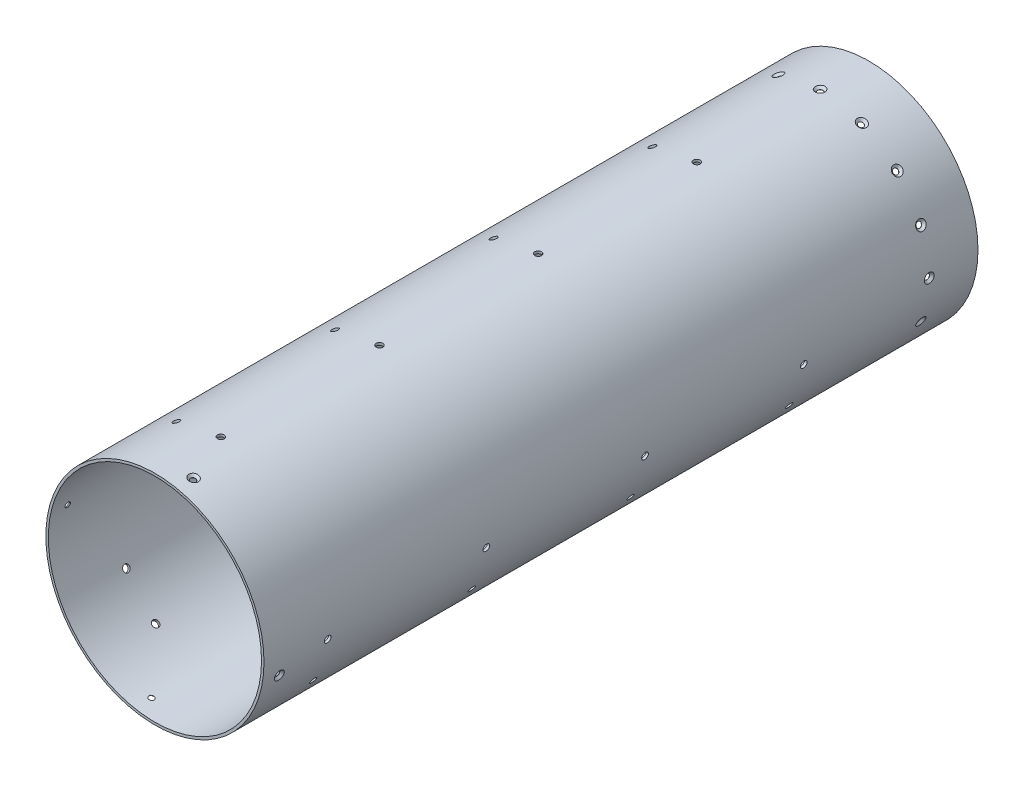
SolidWorks part; units mm, degrees
material "6061-T6 (SS)"
ref_plane "Front Plane" through (0, 0, 0) normal (0, 0, 1) x (1, 0, 0)
ref_plane "Top Plane" through (0, 0, 0) normal (0, 1, 0) x (1, 0, 0)
ref_plane "Right Plane" through (0, 0, 0) normal (1, 0, 0) x (0, 0, -1)
sketch "Sketch1" plane through (0, 0, 0) normal (0, 0, 1) x (1, 0, 0)
  circle A0 centre (0, 0) radius 69.85
  circle A1 centre (0, 0) radius 68.2625
  dimension "D1" = 139.7
  dimension "D2" = 1.5875
extrude "Extrude1" add sketch "Sketch1" along normal blind 457.2
ref_plane "Plane1" through (0, 0, 31.242) normal (0, 0, -1) x (-1, 0, 0)
sketch "Sketch2" plane through (0, 0, 31.242) normal (0, 0, -1) x (-1, 0, 0)
  line L0 (0, 0) -> (0, -69.85) construction
  line L1 (0, 0) -> (-13.6271, -68.5079) construction
  circle A0 centre (0, 0) radius 69.85 construction
  circle A1 centre (0, 0) radius 69.85 construction
  dimension "D1" = 11.25
ref_plane "Plane2" through (0, -69.85, 31.242) normal (0, -1, 0) x (1, 0, 0)
hole_wizard "CSK for M3 Flat Head Machine Screw1" positions "Sketch5" profile "Sketch4" countersink size "M3" standard "Ansi Metric" end condition through all
sketch "Sketch5" plane through (0, -69.85, 31.242) normal (0, -1, 0) x (1, 0, 0)
  point P2 (0, 0)
sketch "Sketch4" plane through (0, -69.85, 31.242) normal (1, 0, 0) x (0, 0, -1)
  line L0 (0, 0) -> (0, 161.1134)
  line L1 (0, 161.1134) -> (1.7, 161.1134)
  line L2 (1.7, 161.1134) -> (1.7, 1.45)
  line L3 (1.7, 1.45) -> (3.15, 0)
  line L5 (3.15, 0) -> (0, 0)
  line L6 (-1.7, 1.45) -> (-3.15, 0) construction
  line L11 (0, -6.35) -> (0, 107.95) construction
  dimension "Thru Hole Dia." = 3.4
  dimension "Thru Hole Depth" = 161.1134
  dimension "Near C'Sink Dia." = 6.3
  dimension "Near C'Sink Angle" = 90
pattern_circular "CirPattern1" count 16 over 360 about axis through (0, 0, 457.2) along (0, 0, -1) of "CSK for M3 Flat Head Machine Screw1"
ref_plane "Plane3" through (0, 0, 446.0875) normal (0, 0, 1) x (1, 0, 0)
ref_plane "Plane5" through (0, 0, 0) normal (0.8315, 0.5556, 0) x (-0.5556, 0.8315, 0)
ref_plane "Plane7" through (0, 0, 0) normal (0.5556, -0.8315, 0) x (0.8315, 0.5556, 0)
ref_plane "Plane9" through (0, 0, 0) normal (-0.1951, -0.9808, 0) x (0.9808, -0.1951, 0)
sketch "Sketch7" plane through (0, 0, 457.2) normal (0, 0, 1) x (1, 0, 0)
  circle A0 centre (0, 0) radius 69.85 construction
  point P0 (69.85, 0)
ref_plane "Plane10" through (13.6271, -68.5079, 31.242) normal (0.1951, -0.9808, 0) x (0.9808, 0.1951, 0)
hole_wizard "#10 Clearance Hole1" positions "Sketch12" profile "Sketch11" hole size "#10" standard "Ansi Inch"
sketch "Sketch12" plane through (13.6271, -68.5079, 31.242) normal (0.1951, -0.9808, 0) x (0.9808, 0.1951, 0)
  point P1 (0, 0)
sketch "Sketch11" plane through (13.6271, -68.5079, 31.242) normal (0, 0, 1) x (0.9808, 0.1951, 0)
  line L0 (0, 0) -> (0, 14.2338)
  line L1 (0, 14.2338) -> (2.5527, 12.7)
  line L2 (2.5527, 12.7) -> (2.5527, 0)
  line L5 (2.5527, 0) -> (0, 0)
  line L10 (0, 14.2338) -> (-2.5527, 12.7) construction
  line L11 (0, -6.35) -> (0, 107.95) construction
  dimension "Hole Dia." = 5.1054
  dimension "Hole Depth" = 12.7
  dimension "Drill Angle" = 118
sketch "Sketch13" plane through (13.6271, -68.5079, 31.242) normal (0.1951, -0.9808, 0) x (0.9808, 0.1951, 0)
  line L0 (0, 0) -> (0, 20.3882) construction
ref_plane "Plane11" through (0, 0, 0) normal (0.9808, 0.1951, 0) x (0, 0, -1)
ref_plane "Plane12" through (0, 0, 446.0748) normal (0, 0, 1) x (1, 0, 0)
sketch "Sketch15" plane through (0, 0, 446.0748) normal (0, 0, 1) x (1, 0, 0)
  line L0 (0, 0) -> (13.6271, 68.5079) construction
  line L2 (0, 0) -> (0, 70.1529) construction
  line L3 (0, 69.8152) -> (0, 68.4) construction
  circle A1 centre (0, 0) radius 69.85 construction
  dimension "D1" = 11.25
ref_plane "Plane13" through (13.6271, 68.5079, 446.0748) normal (0.1951, 0.9808, 0) x (-0.9808, 0.1951, 0)
hole_wizard "CSK for M3 Flat Head Machine Screw2" positions "Sketch17" profile "Sketch16" countersink size "M3" standard "Ansi Metric"
sketch "Sketch17" plane through (13.6271, 68.5079, 446.0748) normal (0.1951, 0.9808, 0) x (-0.9808, 0.1951, 0)
  point P7 (0, 0)
sketch "Sketch16" plane through (13.6271, 68.5079, 446.0748) normal (0, 0, 1) x (-0.9808, 0.1951, 0)
  line L0 (0, 0) -> (0, 8.6415)
  line L1 (0, 8.6415) -> (1.7, 7.62)
  line L2 (1.7, 7.62) -> (1.7, 1.45)
  line L3 (1.7, 1.45) -> (3.15, 0)
  line L5 (3.15, 0) -> (0, 0)
  line L6 (-1.7, 1.45) -> (-3.15, 0) construction
  line L10 (0, 8.6415) -> (-1.7, 7.62) construction
  line L11 (0, -6.35) -> (0, 107.95) construction
  dimension "Hole Dia." = 3.4
  dimension "Hole Depth" = 7.62
  dimension "Near C'Sink Dia." = 6.3
  dimension "Near C'Sink Angle" = 90
  dimension "Drill Angle" = 118
pattern_circular "CirPattern2" count 4 over 360 about axis through (0, 0, 457.2) along (0, 0, -1) of "CSK for M3 Flat Head Machine Screw2"
ref_plane "Plane14" through (0, 0, 415.925) normal (0, 0, 1) x (1, 0, 0)
sketch "Sketch19" plane through (0, 0, 415.925) normal (0, 0, 1) x (1, 0, 0)
  line L0 (0, 0) -> (-16.5084, 82.9932) construction
  line L2 (0, 0) -> (-27.5729, 64.1776) construction
  line L3 (0, 0) -> (0.9143, 69.844) construction
  line L4 (-16.5084, 82.9932) -> (-27.5729, 64.1776) construction
  line L5 (-16.5084, 82.9932) -> (0.9143, 69.844) construction
  line L6 (0, 0) -> (13.6271, -68.5079) construction
  circle A0 centre (0, 0) radius 69.85 construction
  dimension "D1" = 12
ref_plane "Plane15" through (-27.5729, 64.1776, 415.925) normal (-0.3947, 0.9188, 0) x (-0.9188, -0.3947, 0)
ref_plane "Plane16" through (0.9143, 69.844, 415.925) normal (0.0131, 0.9999, 0) x (-0.9999, 0.0131, 0)
hole_wizard "#6 Clearance Hole1" positions "Sketch21" profile "Sketch22" hole size "#6" standard "Ansi Inch"
sketch "Sketch21" plane through (0.9143, 69.844, 415.925) normal (0.0131, 0.9999, 0) x (-0.9999, 0.0131, 0)
  point P3 (0, 0)
sketch "Sketch22" plane through (0.9143, 69.844, 415.925) normal (0, 0, 1) x (-0.9999, 0.0131, 0)
  line L0 (0, 0) -> (0, 13.9934)
  line L1 (0, 13.9934) -> (2.1526, 12.7)
  line L2 (2.1526, 12.7) -> (2.1526, 0)
  line L5 (2.1526, 0) -> (0, 0)
  line L10 (0, 13.9934) -> (-2.1527, 12.7) construction
  line L11 (0, -6.35) -> (0, 107.95) construction
  dimension "Hole Dia." = 4.3053
  dimension "Hole Depth" = 12.7
  dimension "Drill Angle" = 118
hole_wizard "#6 Clearance Hole2" positions "Sketch25" profile "Sketch24" hole size "#6" standard "Ansi Inch"
sketch "Sketch25" plane through (-27.5729, 64.1776, 415.925) normal (-0.3947, 0.9188, 0) x (-0.9188, -0.3947, 0)
  point P1 (0, 0)
sketch "Sketch24" plane through (-27.5729, 64.1776, 415.925) normal (0, 0, 1) x (-0.9188, -0.3947, 0)
  line L0 (0, 0) -> (0, 13.9934)
  line L1 (0, 13.9934) -> (2.1526, 12.7)
  line L2 (2.1526, 12.7) -> (2.1526, 0)
  line L5 (2.1526, 0) -> (0, 0)
  line L10 (0, 13.9934) -> (-2.1526, 12.7) construction
  line L11 (0, -6.35) -> (0, 107.95) construction
  dimension "Hole Dia." = 4.3053
  dimension "Hole Depth" = 12.7
  dimension "Drill Angle" = 118
pattern_circular "CirPattern3" count 3 over 360 about axis through (0, 0, 457.2) along (0, 0, -1) of "#6 Clearance Hole2", "#6 Clearance Hole1"
pattern_linear "LPattern1" count 4 spacing 101.6 along (0, 0, -1) of "#6 Clearance Hole1", "#6 Clearance Hole2", "CirPattern3"
sketch3d "ref hole"
  line L0 (-40.8228, -54.6684, 111.125) -> (-41.7731, -55.941, 111.125) construction
  spline S0 degree 3 poles (-59.8631, -35.9922, 111.4094) (-59.8631, -35.9922, 110.9828) (-59.8703, -35.9802, 110.8429) (-59.8984, -35.9333, 110.5678) (-59.9197, -35.8978, 110.4311) (-59.9752, -35.805, 110.1704) (-60.0091, -35.7482, 110.0468) (-60.0889, -35.6139, 109.8128) (-60.1353, -35.5356, 109.702) (-60.2865, -35.2789, 109.4041) (-60.4076, -35.0715, 109.2438) (-60.6661, -34.6225, 109.029) (-60.8061, -34.3762, 108.9725) (-61.0119, -34.0087, 108.9723) (-61.0812, -33.8841, 108.9862) (-61.2146, -33.6424, 109.0412) (-61.2792, -33.5247, 109.0818) (-61.4038, -33.2958, 109.1895) (-61.4638, -33.1849, 109.2569) (-61.5743, -32.9794, 109.4127) (-61.6256, -32.8835, 109.5017) (-61.72, -32.7059, 109.7025) (-61.7617, -32.627, 109.8114) (-61.8344, -32.489, 110.0445) (-61.8657, -32.4293, 110.1703) (-61.9159, -32.3334, 110.4311) (-61.9347, -32.2973, 110.5653) (-61.9602, -32.2484, 110.8411) (-61.9667, -32.2358, 110.9838) (-61.9668, -32.2358, 111.2647) (-61.9605, -32.2478, 111.4043) (-61.9351, -32.2966, 111.6818) (-61.916, -32.3332, 111.818) (-61.8415, -32.4757, 112.2066) (-61.7669, -32.6176, 112.447) (-61.6273, -32.8803, 112.745) (-61.5751, -32.9778, 112.836) (-61.4643, -33.184, 112.9925) (-61.4055, -33.2927, 113.0587) (-61.281, -33.5213, 113.1669) (-61.2152, -33.6414, 113.2085) (-61.0822, -33.8823, 113.2635) (-61.0143, -34.0044, 113.2775) (-60.8756, -34.2522, 113.2778) (-60.8065, -34.3745, 113.2639) (-60.6707, -34.6137, 113.2095) (-60.6029, -34.7322, 113.1683) (-60.4727, -34.9585, 113.0604) (-60.4106, -35.0656, 112.9944) (-60.2928, -35.2677, 112.8385) (-60.2367, -35.3634, 112.7476) (-60.1358, -35.5348, 112.5491) (-60.0903, -35.6115, 112.4408) (-60.0099, -35.7469, 112.206) (-59.9755, -35.8046, 112.0804) (-59.8926, -35.9432, 111.692) (-59.8631, -35.9922, 111.4094) (-59.8631, -35.9922, 110.9828) (-59.8703, -35.9802, 110.8429) knots -0.0625 -0.0625 0 0 0.03125 0.03125 0.0625 0.0625 0.09375 0.09375 0.125 0.125 0.1875 0.1875 0.25 0.25 0.28125 0.28125 0.3125 0.3125 0.34375 0.34375 0.375 0.375 0.40625 0.40625 0.4375 0.4375 0.46875 0.46875 0.5 0.5 0.53125 0.53125 0.5625 0.5625 0.625 0.625 0.65625 0.65625 0.6875 0.6875 0.71875 0.71875 0.75 0.75 0.78125 0.78125 0.8125 0.8125 0.84375 0.84375 0.875 0.875 0.90625 0.90625 0.9375 0.9375 1 1 1.03125 1.03125 1.0625 only from (-59.8631, -35.9922, 111.125) to (-59.8631, -35.9922, 111.125) construction
  spline S1 degree 3 poles (-40.0483, -57.229, 111.4094) (-40.0483, -57.229, 110.9828) (-40.0597, -57.221, 110.8429) (-40.1045, -57.1896, 110.5678) (-40.1385, -57.1658, 110.4311) (-40.2269, -57.1036, 110.1704) (-40.2809, -57.0655, 110.0468) (-40.4085, -56.9753, 109.8128) (-40.4827, -56.9226, 109.702) (-40.7253, -56.7496, 109.4041) (-40.9203, -56.6094, 109.2438) (-41.339, -56.3043, 109.029) (-41.5671, -56.1363, 108.9725) (-41.9045, -55.8843, 108.9723) (-42.0185, -55.7986, 108.9862) (-42.2388, -55.6321, 109.0412) (-42.3456, -55.5508, 109.0818) (-42.5526, -55.3924, 109.1895) (-42.6525, -55.3155, 109.2569) (-42.837, -55.1727, 109.4127) (-42.9228, -55.1059, 109.5017) (-43.0813, -54.9821, 109.7025) (-43.1515, -54.927, 109.8114) (-43.2741, -54.8305, 110.0445) (-43.327, -54.7887, 110.1703) (-43.4118, -54.7215, 110.4311) (-43.4437, -54.6962, 110.5653) (-43.4868, -54.6618, 110.8411) (-43.4979, -54.653, 110.9838) (-43.498, -54.653, 111.2647) (-43.4874, -54.6614, 111.4043) (-43.4443, -54.6956, 111.6818) (-43.412, -54.7213, 111.818) (-43.2859, -54.8212, 112.2066) (-43.1601, -54.9205, 112.447) (-42.9257, -55.1037, 112.745) (-42.8384, -55.1716, 112.836) (-42.6532, -55.3149, 112.9925) (-42.5553, -55.3903, 113.0587) (-42.3486, -55.5485, 113.1669) (-42.2397, -55.6314, 113.2085) (-42.0202, -55.7974, 113.2635) (-41.9085, -55.8813, 113.2775) (-41.681, -56.0512, 113.2778) (-41.5682, -56.1349, 113.2639) (-41.3468, -56.2982, 113.2095) (-41.2367, -56.3789, 113.1683) (-41.0256, -56.5326, 113.0604) (-40.9254, -56.6052, 112.9944) (-40.7356, -56.742, 112.8385) (-40.6454, -56.8066, 112.7476) (-40.4834, -56.9221, 112.5491) (-40.4107, -56.9737, 112.4408) (-40.2822, -57.0646, 112.206) (-40.2273, -57.1033, 112.0804) (-40.0952, -57.1962, 111.692) (-40.0483, -57.229, 111.4094) (-40.0483, -57.229, 110.9828) (-40.0597, -57.221, 110.8429) knots -0.0625 -0.0625 0 0 0.03125 0.03125 0.0625 0.0625 0.09375 0.09375 0.125 0.125 0.1875 0.1875 0.25 0.25 0.28125 0.28125 0.3125 0.3125 0.34375 0.34375 0.375 0.375 0.40625 0.40625 0.4375 0.4375 0.46875 0.46875 0.5 0.5 0.53125 0.53125 0.5625 0.5625 0.625 0.625 0.65625 0.65625 0.6875 0.6875 0.71875 0.71875 0.75 0.75 0.78125 0.78125 0.8125 0.8125 0.84375 0.84375 0.875 0.875 0.90625 0.90625 0.9375 0.9375 1 1 1.03125 1.03125 1.0625 only from (-40.0483, -57.229, 111.125) to (-40.0483, -57.229, 111.125) construction
  spline S2 degree 3 poles (-59.8631, -35.9922, 111.4094) (-59.8631, -35.9922, 110.9828) (-59.8703, -35.9802, 110.8429) (-59.8984, -35.9333, 110.5678) (-59.9197, -35.8978, 110.4311) (-59.9752, -35.805, 110.1704) (-60.0091, -35.7482, 110.0468) (-60.0889, -35.6139, 109.8128) (-60.1353, -35.5356, 109.702) (-60.2865, -35.2789, 109.4041) (-60.4076, -35.0715, 109.2438) (-60.6661, -34.6225, 109.029) (-60.8061, -34.3762, 108.9725) (-61.0119, -34.0087, 108.9723) (-61.0812, -33.8841, 108.9862) (-61.2146, -33.6424, 109.0412) (-61.2792, -33.5247, 109.0818) (-61.4038, -33.2958, 109.1895) (-61.4638, -33.1849, 109.2569) (-61.5743, -32.9794, 109.4127) (-61.6256, -32.8835, 109.5017) (-61.72, -32.7059, 109.7025) (-61.7617, -32.627, 109.8114) (-61.8344, -32.489, 110.0445) (-61.8657, -32.4293, 110.1703) (-61.9159, -32.3334, 110.4311) (-61.9347, -32.2973, 110.5653) (-61.9602, -32.2484, 110.8411) (-61.9667, -32.2358, 110.9838) (-61.9668, -32.2358, 111.2647) (-61.9605, -32.2478, 111.4043) (-61.9351, -32.2966, 111.6818) (-61.916, -32.3332, 111.818) (-61.8415, -32.4757, 112.2066) (-61.7669, -32.6176, 112.447) (-61.6273, -32.8803, 112.745) (-61.5751, -32.9778, 112.836) (-61.4643, -33.184, 112.9925) (-61.4055, -33.2927, 113.0587) (-61.281, -33.5213, 113.1669) (-61.2152, -33.6414, 113.2085) (-61.0822, -33.8823, 113.2635) (-61.0143, -34.0044, 113.2775) (-60.8756, -34.2522, 113.2778) (-60.8065, -34.3745, 113.2639) (-60.6707, -34.6137, 113.2095) (-60.6029, -34.7322, 113.1683) (-60.4727, -34.9585, 113.0604) (-60.4106, -35.0656, 112.9944) (-60.2928, -35.2677, 112.8385) (-60.2367, -35.3634, 112.7476) (-60.1358, -35.5348, 112.5491) (-60.0903, -35.6115, 112.4408) (-60.0099, -35.7469, 112.206) (-59.9755, -35.8046, 112.0804) (-59.8926, -35.9432, 111.692) (-59.8631, -35.9922, 111.4094) (-59.8631, -35.9922, 110.9828) (-59.8703, -35.9802, 110.8429) knots -0.0625 -0.0625 0 0 0.03125 0.03125 0.0625 0.0625 0.09375 0.09375 0.125 0.125 0.1875 0.1875 0.25 0.25 0.28125 0.28125 0.3125 0.3125 0.34375 0.34375 0.375 0.375 0.40625 0.40625 0.4375 0.4375 0.46875 0.46875 0.5 0.5 0.53125 0.53125 0.5625 0.5625 0.625 0.625 0.65625 0.65625 0.6875 0.6875 0.71875 0.71875 0.75 0.75 0.78125 0.78125 0.8125 0.8125 0.84375 0.84375 0.875 0.875 0.90625 0.90625 0.9375 0.9375 1 1 1.03125 1.03125 1.0625 only from (-59.8631, -35.9922, 111.125) to (-59.8631, -35.9922, 111.125)
  spline S3 degree 3 poles (-40.0483, -57.229, 111.4094) (-40.0483, -57.229, 110.9828) (-40.0597, -57.221, 110.8429) (-40.1045, -57.1896, 110.5678) (-40.1385, -57.1658, 110.4311) (-40.2269, -57.1036, 110.1704) (-40.2809, -57.0655, 110.0468) (-40.4085, -56.9753, 109.8128) (-40.4827, -56.9226, 109.702) (-40.7253, -56.7496, 109.4041) (-40.9203, -56.6094, 109.2438) (-41.339, -56.3043, 109.029) (-41.5671, -56.1363, 108.9725) (-41.9045, -55.8843, 108.9723) (-42.0185, -55.7986, 108.9862) (-42.2388, -55.6321, 109.0412) (-42.3456, -55.5508, 109.0818) (-42.5526, -55.3924, 109.1895) (-42.6525, -55.3155, 109.2569) (-42.837, -55.1727, 109.4127) (-42.9228, -55.1059, 109.5017) (-43.0813, -54.9821, 109.7025) (-43.1515, -54.927, 109.8114) (-43.2741, -54.8305, 110.0445) (-43.327, -54.7887, 110.1703) (-43.4118, -54.7215, 110.4311) (-43.4437, -54.6962, 110.5653) (-43.4868, -54.6618, 110.8411) (-43.4979, -54.653, 110.9838) (-43.498, -54.653, 111.2647) (-43.4874, -54.6614, 111.4043) (-43.4443, -54.6956, 111.6818) (-43.412, -54.7213, 111.818) (-43.2859, -54.8212, 112.2066) (-43.1601, -54.9205, 112.447) (-42.9257, -55.1037, 112.745) (-42.8384, -55.1716, 112.836) (-42.6532, -55.3149, 112.9925) (-42.5553, -55.3903, 113.0587) (-42.3486, -55.5485, 113.1669) (-42.2397, -55.6314, 113.2085) (-42.0202, -55.7974, 113.2635) (-41.9085, -55.8813, 113.2775) (-41.681, -56.0512, 113.2778) (-41.5682, -56.1349, 113.2639) (-41.3468, -56.2982, 113.2095) (-41.2367, -56.3789, 113.1683) (-41.0256, -56.5326, 113.0604) (-40.9254, -56.6052, 112.9944) (-40.7356, -56.742, 112.8385) (-40.6454, -56.8066, 112.7476) (-40.4834, -56.9221, 112.5491) (-40.4107, -56.9737, 112.4408) (-40.2822, -57.0646, 112.206) (-40.2273, -57.1033, 112.0804) (-40.0952, -57.1962, 111.692) (-40.0483, -57.229, 111.4094) (-40.0483, -57.229, 110.9828) (-40.0597, -57.221, 110.8429) knots -0.0625 -0.0625 0 0 0.03125 0.03125 0.0625 0.0625 0.09375 0.09375 0.125 0.125 0.1875 0.1875 0.25 0.25 0.28125 0.28125 0.3125 0.3125 0.34375 0.34375 0.375 0.375 0.40625 0.40625 0.4375 0.4375 0.46875 0.46875 0.5 0.5 0.53125 0.53125 0.5625 0.5625 0.625 0.625 0.65625 0.65625 0.6875 0.6875 0.71875 0.71875 0.75 0.75 0.78125 0.78125 0.8125 0.8125 0.84375 0.84375 0.875 0.875 0.90625 0.90625 0.9375 0.9375 1 1 1.03125 1.03125 1.0625 only from (-40.0483, -57.229, 111.125) to (-40.0483, -57.229, 111.125)
  spline S4 degree 3 poles (61.1017, -33.8469, 314.6094) (61.1017, -33.8469, 314.1828) (61.0949, -33.8591, 314.0429) (61.0684, -33.9069, 313.7678) (61.0483, -33.9431, 313.6311) (60.9957, -34.0376, 313.3704) (60.9634, -34.0953, 313.2468) (60.887, -34.2316, 313.0128) (60.8424, -34.3109, 312.902) (60.6957, -34.5702, 312.6041) (60.5766, -34.7788, 312.4438) (60.317, -35.2271, 312.229) (60.1737, -35.4715, 312.1725) (59.9583, -35.8335, 312.1723) (59.8851, -35.9558, 312.1862) (59.7425, -36.1923, 312.2412) (59.6728, -36.307, 312.2818) (59.5369, -36.5294, 312.3895) (59.4709, -36.6368, 312.4569) (59.3481, -36.8352, 312.6127) (59.2907, -36.9276, 312.7017) (59.1841, -37.0981, 312.9025) (59.1367, -37.1737, 313.0114) (59.0535, -37.3057, 313.2445) (59.0174, -37.3627, 313.3703) (58.9595, -37.454, 313.6311) (58.9376, -37.4884, 313.7653) (58.908, -37.5349, 314.0411) (58.9004, -37.5468, 314.1838) (58.9004, -37.5469, 314.4647) (58.9077, -37.5355, 314.6043) (58.9372, -37.4891, 314.8818) (58.9594, -37.4542, 315.018) (59.0455, -37.3184, 315.4066) (59.1311, -37.1829, 315.647) (59.2888, -36.9306, 315.945) (59.3472, -36.8367, 316.036) (59.4703, -36.6376, 316.1925) (59.5351, -36.5323, 316.2587) (59.6708, -36.3102, 316.3669) (59.7419, -36.1932, 316.4085) (59.884, -35.9576, 316.4635) (59.9558, -35.8377, 316.4775) (60.101, -35.5937, 316.4778) (60.1725, -35.4728, 316.4639) (60.3117, -35.2355, 316.4095) (60.3804, -35.1176, 316.3683) (60.5113, -34.8916, 316.2604) (60.573, -34.7843, 316.1944) (60.6891, -34.5813, 316.0385) (60.744, -34.4848, 315.9476) (60.8419, -34.3117, 315.7491) (60.8857, -34.234, 315.6408) (60.9627, -34.0967, 315.406) (60.9954, -34.038, 315.2804) (61.074, -33.8969, 314.892) (61.1017, -33.8469, 314.6094) (61.1017, -33.8469, 314.1828) (61.0949, -33.8591, 314.0429) knots -0.0625 -0.0625 0 0 0.03125 0.03125 0.0625 0.0625 0.09375 0.09375 0.125 0.125 0.1875 0.1875 0.25 0.25 0.28125 0.28125 0.3125 0.3125 0.34375 0.34375 0.375 0.375 0.40625 0.40625 0.4375 0.4375 0.46875 0.46875 0.5 0.5 0.53125 0.53125 0.5625 0.5625 0.625 0.625 0.65625 0.65625 0.6875 0.6875 0.71875 0.71875 0.75 0.75 0.78125 0.78125 0.8125 0.8125 0.84375 0.84375 0.875 0.875 0.90625 0.90625 0.9375 0.9375 1 1 1.03125 1.03125 1.0625 only from (61.1017, -33.8469, 314.325) to (61.1017, -33.8469, 314.325) construction
  spline S5 degree 3 poles (-59.8631, -35.9922, 314.6094) (-59.8631, -35.9922, 314.1828) (-59.8703, -35.9802, 314.0429) (-59.8984, -35.9333, 313.7678) (-59.9197, -35.8978, 313.6311) (-59.9752, -35.805, 313.3704) (-60.0091, -35.7482, 313.2468) (-60.0889, -35.6139, 313.0128) (-60.1353, -35.5356, 312.902) (-60.2865, -35.2789, 312.6041) (-60.4076, -35.0715, 312.4438) (-60.6661, -34.6225, 312.229) (-60.8061, -34.3762, 312.1725) (-61.0119, -34.0087, 312.1723) (-61.0812, -33.8841, 312.1862) (-61.2146, -33.6424, 312.2412) (-61.2792, -33.5247, 312.2818) (-61.4038, -33.2958, 312.3895) (-61.4638, -33.1849, 312.4569) (-61.5743, -32.9794, 312.6127) (-61.6256, -32.8835, 312.7017) (-61.72, -32.7059, 312.9025) (-61.7617, -32.627, 313.0114) (-61.8344, -32.489, 313.2445) (-61.8657, -32.4293, 313.3703) (-61.9159, -32.3334, 313.6311) (-61.9347, -32.2973, 313.7653) (-61.9602, -32.2484, 314.0411) (-61.9667, -32.2358, 314.1838) (-61.9668, -32.2358, 314.4647) (-61.9605, -32.2478, 314.6043) (-61.9351, -32.2966, 314.8818) (-61.916, -32.3332, 315.018) (-61.8415, -32.4757, 315.4066) (-61.7669, -32.6176, 315.647) (-61.6273, -32.8803, 315.945) (-61.5751, -32.9778, 316.036) (-61.4643, -33.184, 316.1925) (-61.4055, -33.2927, 316.2587) (-61.281, -33.5213, 316.3669) (-61.2152, -33.6414, 316.4085) (-61.0822, -33.8823, 316.4635) (-61.0143, -34.0044, 316.4775) (-60.8756, -34.2522, 316.4778) (-60.8065, -34.3745, 316.4639) (-60.6707, -34.6137, 316.4095) (-60.6029, -34.7322, 316.3683) (-60.4727, -34.9585, 316.2604) (-60.4106, -35.0656, 316.1944) (-60.2928, -35.2677, 316.0385) (-60.2367, -35.3634, 315.9476) (-60.1358, -35.5348, 315.7491) (-60.0903, -35.6115, 315.6408) (-60.0099, -35.7469, 315.406) (-59.9755, -35.8046, 315.2804) (-59.8926, -35.9432, 314.892) (-59.8631, -35.9922, 314.6094) (-59.8631, -35.9922, 314.1828) (-59.8703, -35.9802, 314.0429) knots -0.0625 -0.0625 0 0 0.03125 0.03125 0.0625 0.0625 0.09375 0.09375 0.125 0.125 0.1875 0.1875 0.25 0.25 0.28125 0.28125 0.3125 0.3125 0.34375 0.34375 0.375 0.375 0.40625 0.40625 0.4375 0.4375 0.46875 0.46875 0.5 0.5 0.53125 0.53125 0.5625 0.5625 0.625 0.625 0.65625 0.65625 0.6875 0.6875 0.71875 0.71875 0.75 0.75 0.78125 0.78125 0.8125 0.8125 0.84375 0.84375 0.875 0.875 0.90625 0.90625 0.9375 0.9375 1 1 1.03125 1.03125 1.0625 only from (-59.8631, -35.9922, 314.325) to (-59.8631, -35.9922, 314.325) construction
  spline S6 degree 3 poles (-40.0483, -57.229, 314.6094) (-40.0483, -57.229, 314.1828) (-40.0597, -57.221, 314.0429) (-40.1045, -57.1896, 313.7678) (-40.1385, -57.1658, 313.6311) (-40.2269, -57.1036, 313.3704) (-40.2809, -57.0655, 313.2468) (-40.4085, -56.9753, 313.0128) (-40.4827, -56.9226, 312.902) (-40.7253, -56.7496, 312.6041) (-40.9203, -56.6094, 312.4438) (-41.339, -56.3043, 312.229) (-41.5671, -56.1363, 312.1725) (-41.9045, -55.8843, 312.1723) (-42.0185, -55.7986, 312.1862) (-42.2388, -55.6321, 312.2412) (-42.3456, -55.5508, 312.2818) (-42.5526, -55.3924, 312.3895) (-42.6525, -55.3155, 312.4569) (-42.837, -55.1727, 312.6127) (-42.9228, -55.1059, 312.7017) (-43.0813, -54.9821, 312.9025) (-43.1515, -54.927, 313.0114) (-43.2741, -54.8305, 313.2445) (-43.327, -54.7887, 313.3703) (-43.4118, -54.7215, 313.6311) (-43.4437, -54.6962, 313.7653) (-43.4868, -54.6618, 314.0411) (-43.4979, -54.653, 314.1838) (-43.498, -54.653, 314.4647) (-43.4874, -54.6614, 314.6043) (-43.4443, -54.6956, 314.8818) (-43.412, -54.7213, 315.018) (-43.2859, -54.8212, 315.4066) (-43.1601, -54.9205, 315.647) (-42.9257, -55.1037, 315.945) (-42.8384, -55.1716, 316.036) (-42.6532, -55.3149, 316.1925) (-42.5553, -55.3903, 316.2587) (-42.3486, -55.5485, 316.3669) (-42.2397, -55.6314, 316.4085) (-42.0202, -55.7974, 316.4635) (-41.9085, -55.8813, 316.4775) (-41.681, -56.0512, 316.4778) (-41.5682, -56.1349, 316.4639) (-41.3468, -56.2982, 316.4095) (-41.2367, -56.3789, 316.3683) (-41.0256, -56.5326, 316.2604) (-40.9254, -56.6052, 316.1944) (-40.7356, -56.742, 316.0385) (-40.6454, -56.8066, 315.9476) (-40.4834, -56.9221, 315.7491) (-40.4107, -56.9737, 315.6408) (-40.2822, -57.0646, 315.406) (-40.2273, -57.1033, 315.2804) (-40.0952, -57.1962, 314.892) (-40.0483, -57.229, 314.6094) (-40.0483, -57.229, 314.1828) (-40.0597, -57.221, 314.0429) knots -0.0625 -0.0625 0 0 0.03125 0.03125 0.0625 0.0625 0.09375 0.09375 0.125 0.125 0.1875 0.1875 0.25 0.25 0.28125 0.28125 0.3125 0.3125 0.34375 0.34375 0.375 0.375 0.40625 0.40625 0.4375 0.4375 0.46875 0.46875 0.5 0.5 0.53125 0.53125 0.5625 0.5625 0.625 0.625 0.65625 0.65625 0.6875 0.6875 0.71875 0.71875 0.75 0.75 0.78125 0.78125 0.8125 0.8125 0.84375 0.84375 0.875 0.875 0.90625 0.90625 0.9375 0.9375 1 1 1.03125 1.03125 1.0625 only from (-40.0483, -57.229, 314.325) to (-40.0483, -57.229, 314.325) construction
  spline S7 degree 3 poles (61.1017, -33.8469, 314.6094) (61.1017, -33.8469, 314.1828) (61.0949, -33.8591, 314.0429) (61.0684, -33.9069, 313.7678) (61.0483, -33.9431, 313.6311) (60.9957, -34.0376, 313.3704) (60.9634, -34.0953, 313.2468) (60.887, -34.2316, 313.0128) (60.8424, -34.3109, 312.902) (60.6957, -34.5702, 312.6041) (60.5766, -34.7788, 312.4438) (60.317, -35.2271, 312.229) (60.1737, -35.4715, 312.1725) (59.9583, -35.8335, 312.1723) (59.8851, -35.9558, 312.1862) (59.7425, -36.1923, 312.2412) (59.6728, -36.307, 312.2818) (59.5369, -36.5294, 312.3895) (59.4709, -36.6368, 312.4569) (59.3481, -36.8352, 312.6127) (59.2907, -36.9276, 312.7017) (59.1841, -37.0981, 312.9025) (59.1367, -37.1737, 313.0114) (59.0535, -37.3057, 313.2445) (59.0174, -37.3627, 313.3703) (58.9595, -37.454, 313.6311) (58.9376, -37.4884, 313.7653) (58.908, -37.5349, 314.0411) (58.9004, -37.5468, 314.1838) (58.9004, -37.5469, 314.4647) (58.9077, -37.5355, 314.6043) (58.9372, -37.4891, 314.8818) (58.9594, -37.4542, 315.018) (59.0455, -37.3184, 315.4066) (59.1311, -37.1829, 315.647) (59.2888, -36.9306, 315.945) (59.3472, -36.8367, 316.036) (59.4703, -36.6376, 316.1925) (59.5351, -36.5323, 316.2587) (59.6708, -36.3102, 316.3669) (59.7419, -36.1932, 316.4085) (59.884, -35.9576, 316.4635) (59.9558, -35.8377, 316.4775) (60.101, -35.5937, 316.4778) (60.1725, -35.4728, 316.4639) (60.3117, -35.2355, 316.4095) (60.3804, -35.1176, 316.3683) (60.5113, -34.8916, 316.2604) (60.573, -34.7843, 316.1944) (60.6891, -34.5813, 316.0385) (60.744, -34.4848, 315.9476) (60.8419, -34.3117, 315.7491) (60.8857, -34.234, 315.6408) (60.9627, -34.0967, 315.406) (60.9954, -34.038, 315.2804) (61.074, -33.8969, 314.892) (61.1017, -33.8469, 314.6094) (61.1017, -33.8469, 314.1828) (61.0949, -33.8591, 314.0429) knots -0.0625 -0.0625 0 0 0.03125 0.03125 0.0625 0.0625 0.09375 0.09375 0.125 0.125 0.1875 0.1875 0.25 0.25 0.28125 0.28125 0.3125 0.3125 0.34375 0.34375 0.375 0.375 0.40625 0.40625 0.4375 0.4375 0.46875 0.46875 0.5 0.5 0.53125 0.53125 0.5625 0.5625 0.625 0.625 0.65625 0.65625 0.6875 0.6875 0.71875 0.71875 0.75 0.75 0.78125 0.78125 0.8125 0.8125 0.84375 0.84375 0.875 0.875 0.90625 0.90625 0.9375 0.9375 1 1 1.03125 1.03125 1.0625 only from (61.1017, -33.8469, 314.325) to (61.1017, -33.8469, 314.325)
  spline S8 degree 3 poles (-59.8631, -35.9922, 314.6094) (-59.8631, -35.9922, 314.1828) (-59.8703, -35.9802, 314.0429) (-59.8984, -35.9333, 313.7678) (-59.9197, -35.8978, 313.6311) (-59.9752, -35.805, 313.3704) (-60.0091, -35.7482, 313.2468) (-60.0889, -35.6139, 313.0128) (-60.1353, -35.5356, 312.902) (-60.2865, -35.2789, 312.6041) (-60.4076, -35.0715, 312.4438) (-60.6661, -34.6225, 312.229) (-60.8061, -34.3762, 312.1725) (-61.0119, -34.0087, 312.1723) (-61.0812, -33.8841, 312.1862) (-61.2146, -33.6424, 312.2412) (-61.2792, -33.5247, 312.2818) (-61.4038, -33.2958, 312.3895) (-61.4638, -33.1849, 312.4569) (-61.5743, -32.9794, 312.6127) (-61.6256, -32.8835, 312.7017) (-61.72, -32.7059, 312.9025) (-61.7617, -32.627, 313.0114) (-61.8344, -32.489, 313.2445) (-61.8657, -32.4293, 313.3703) (-61.9159, -32.3334, 313.6311) (-61.9347, -32.2973, 313.7653) (-61.9602, -32.2484, 314.0411) (-61.9667, -32.2358, 314.1838) (-61.9668, -32.2358, 314.4647) (-61.9605, -32.2478, 314.6043) (-61.9351, -32.2966, 314.8818) (-61.916, -32.3332, 315.018) (-61.8415, -32.4757, 315.4066) (-61.7669, -32.6176, 315.647) (-61.6273, -32.8803, 315.945) (-61.5751, -32.9778, 316.036) (-61.4643, -33.184, 316.1925) (-61.4055, -33.2927, 316.2587) (-61.281, -33.5213, 316.3669) (-61.2152, -33.6414, 316.4085) (-61.0822, -33.8823, 316.4635) (-61.0143, -34.0044, 316.4775) (-60.8756, -34.2522, 316.4778) (-60.8065, -34.3745, 316.4639) (-60.6707, -34.6137, 316.4095) (-60.6029, -34.7322, 316.3683) (-60.4727, -34.9585, 316.2604) (-60.4106, -35.0656, 316.1944) (-60.2928, -35.2677, 316.0385) (-60.2367, -35.3634, 315.9476) (-60.1358, -35.5348, 315.7491) (-60.0903, -35.6115, 315.6408) (-60.0099, -35.7469, 315.406) (-59.9755, -35.8046, 315.2804) (-59.8926, -35.9432, 314.892) (-59.8631, -35.9922, 314.6094) (-59.8631, -35.9922, 314.1828) (-59.8703, -35.9802, 314.0429) knots -0.0625 -0.0625 0 0 0.03125 0.03125 0.0625 0.0625 0.09375 0.09375 0.125 0.125 0.1875 0.1875 0.25 0.25 0.28125 0.28125 0.3125 0.3125 0.34375 0.34375 0.375 0.375 0.40625 0.40625 0.4375 0.4375 0.46875 0.46875 0.5 0.5 0.53125 0.53125 0.5625 0.5625 0.625 0.625 0.65625 0.65625 0.6875 0.6875 0.71875 0.71875 0.75 0.75 0.78125 0.78125 0.8125 0.8125 0.84375 0.84375 0.875 0.875 0.90625 0.90625 0.9375 0.9375 1 1 1.03125 1.03125 1.0625 only from (-59.8631, -35.9922, 314.325) to (-59.8631, -35.9922, 314.325)
  spline S9 degree 3 poles (-40.0483, -57.229, 314.6094) (-40.0483, -57.229, 314.1828) (-40.0597, -57.221, 314.0429) (-40.1045, -57.1896, 313.7678) (-40.1385, -57.1658, 313.6311) (-40.2269, -57.1036, 313.3704) (-40.2809, -57.0655, 313.2468) (-40.4085, -56.9753, 313.0128) (-40.4827, -56.9226, 312.902) (-40.7253, -56.7496, 312.6041) (-40.9203, -56.6094, 312.4438) (-41.339, -56.3043, 312.229) (-41.5671, -56.1363, 312.1725) (-41.9045, -55.8843, 312.1723) (-42.0185, -55.7986, 312.1862) (-42.2388, -55.6321, 312.2412) (-42.3456, -55.5508, 312.2818) (-42.5526, -55.3924, 312.3895) (-42.6525, -55.3155, 312.4569) (-42.837, -55.1727, 312.6127) (-42.9228, -55.1059, 312.7017) (-43.0813, -54.9821, 312.9025) (-43.1515, -54.927, 313.0114) (-43.2741, -54.8305, 313.2445) (-43.327, -54.7887, 313.3703) (-43.4118, -54.7215, 313.6311) (-43.4437, -54.6962, 313.7653) (-43.4868, -54.6618, 314.0411) (-43.4979, -54.653, 314.1838) (-43.498, -54.653, 314.4647) (-43.4874, -54.6614, 314.6043) (-43.4443, -54.6956, 314.8818) (-43.412, -54.7213, 315.018) (-43.2859, -54.8212, 315.4066) (-43.1601, -54.9205, 315.647) (-42.9257, -55.1037, 315.945) (-42.8384, -55.1716, 316.036) (-42.6532, -55.3149, 316.1925) (-42.5553, -55.3903, 316.2587) (-42.3486, -55.5485, 316.3669) (-42.2397, -55.6314, 316.4085) (-42.0202, -55.7974, 316.4635) (-41.9085, -55.8813, 316.4775) (-41.681, -56.0512, 316.4778) (-41.5682, -56.1349, 316.4639) (-41.3468, -56.2982, 316.4095) (-41.2367, -56.3789, 316.3683) (-41.0256, -56.5326, 316.2604) (-40.9254, -56.6052, 316.1944) (-40.7356, -56.742, 316.0385) (-40.6454, -56.8066, 315.9476) (-40.4834, -56.9221, 315.7491) (-40.4107, -56.9737, 315.6408) (-40.2822, -57.0646, 315.406) (-40.2273, -57.1033, 315.2804) (-40.0952, -57.1962, 314.892) (-40.0483, -57.229, 314.6094) (-40.0483, -57.229, 314.1828) (-40.0597, -57.221, 314.0429) knots -0.0625 -0.0625 0 0 0.03125 0.03125 0.0625 0.0625 0.09375 0.09375 0.125 0.125 0.1875 0.1875 0.25 0.25 0.28125 0.28125 0.3125 0.3125 0.34375 0.34375 0.375 0.375 0.40625 0.40625 0.4375 0.4375 0.46875 0.46875 0.5 0.5 0.53125 0.53125 0.5625 0.5625 0.625 0.625 0.65625 0.65625 0.6875 0.6875 0.71875 0.71875 0.75 0.75 0.78125 0.78125 0.8125 0.8125 0.84375 0.84375 0.875 0.875 0.90625 0.90625 0.9375 0.9375 1 1 1.03125 1.03125 1.0625 only from (-40.0483, -57.229, 314.325) to (-40.0483, -57.229, 314.325)
  point P2 (-41.7437, -55.9017, 111.125)
